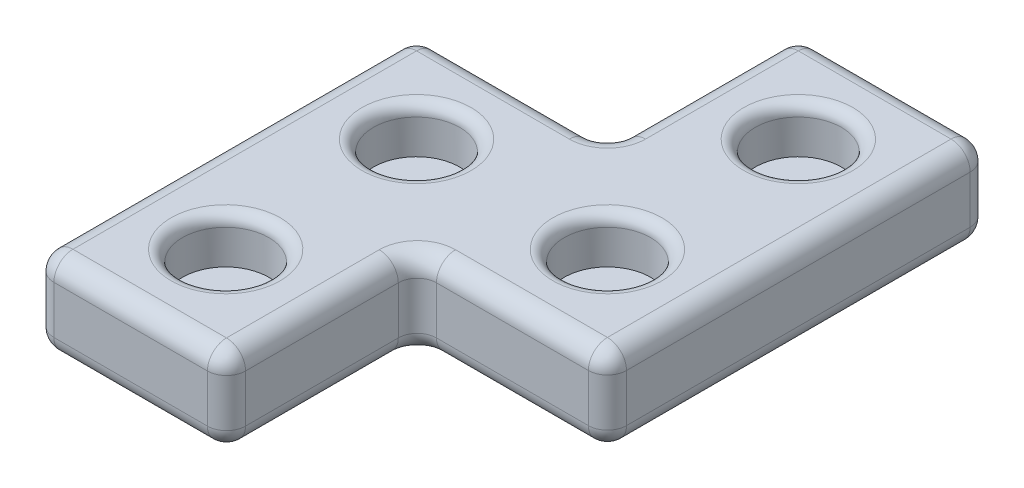
SolidWorks part; units mm, degrees
ref_plane "Front Plane" through (0, 0, 0) normal (0, 0, 1) x (1, 0, 0)
ref_plane "Top Plane" through (0, 0, 0) normal (0, 1, 0) x (1, 0, 0)
ref_plane "Right Plane" through (0, 0, 0) normal (1, 0, 0) x (0, 0, -1)
sketch "Sketch1" plane through (0, 0, 0) normal (0, 1, 0) x (1, 0, 0)
  line L0 (-7.6659, 2.6651) -> (-7.6659, 12.8251)
  line L1 (-6.3959, 14.0951) -> (3.7641, 14.0951)
  line L2 (5.0341, 12.8251) -> (5.0341, -10.0349)
  line L3 (3.7641, -11.3049) -> (-6.3409, -11.3049)
  line L4 (-7.6109, -12.5749) -> (-7.6109, -22.7349)
  line L5 (-8.8809, -24.0049) -> (-19.0959, -24.0049)
  line L6 (-20.3659, -22.7349) -> (-20.3659, 0.1251)
  line L7 (-19.0959, 1.3951) -> (-8.9359, 1.3951)
  arc A0 (-7.6659, 2.6651) -> (-8.9359, 1.3951) centre (-8.9359, 2.6651) cw
  arc A1 (-6.3409, -11.3049) -> (-7.6109, -12.5749) centre (-6.3409, -12.5749) ccw
  arc A2 (-7.6109, -22.7349) -> (-8.8809, -24.0049) centre (-8.8809, -22.7349) cw
  arc A3 (-19.0959, -24.0049) -> (-20.3659, -22.7349) centre (-19.0959, -22.7349) cw
  arc A4 (-20.3659, 0.1251) -> (-19.0959, 1.3951) centre (-19.0959, 0.1251) cw
  arc A5 (5.0341, -10.0349) -> (3.7641, -11.3049) centre (3.7641, -10.0349) cw
  arc A6 (-7.6659, 12.8251) -> (-6.3959, 14.0951) centre (-6.3959, 12.8251) cw
  arc A7 (3.7641, 14.0951) -> (5.0341, 12.8251) centre (3.7641, 12.8251) cw
  point P10 (-7.6659, 1.3951)
  point P13 (-7.6109, -11.3049)
  point P18 (-20.3659, -24.0049)
  point P21 (-20.3659, 1.3951)
  point P24 (5.0341, -11.3049)
  point P27 (-7.6659, 14.0951)
  point P30 (5.0341, 14.0951)
  dimension "D7" = 1.27
  dimension "D1" = 12.7
  dimension "D2" = 25.4
  dimension "D3" = 12.7
  dimension "D4" = 25.4
  dimension "D5" = 12.645
  dimension "D6" = 12.7
extrude "Boss-Extrude1" add sketch "Sketch1" along normal blind 5.715
sketch "Sketch2" plane through (0, 5.715, 0) normal (0, 1, 0) x (1, 0, 0)
  line L0 (5.0341, -10.0349) -> (5.0341, 12.8251) construction
  line L1 (-19.0959, -24.0049) -> (-8.8809, -24.0049) construction
  circle A0 centre (-1.3159, 7.7451) radius 2.8702
  circle A1 centre (-14.0159, -4.9549) radius 2.8702
  circle A2 centre (-14.0159, -17.6549) radius 2.8702
  circle A3 centre (-1.3159, -4.9549) radius 2.8702
  dimension "D1" = 6.35
  dimension "D2" = 12.7
  dimension "D3" = 12.7
  dimension "D4" = 12.7
  dimension "D5" = 6.35
extrude "Cut-Extrude1" cut sketch "Sketch2" against normal blind 3.048
fillet "Fillet1" radius 1.27 16 edges at (-1.2884, 5.715, 11.3049) (-7.6109, 5.715, 17.6549) (-13.9884, 5.715, 24.0049) (-20.3659, 5.715, 11.3049) (-14.0159, 5.715, -1.3951) (-7.6659, 5.715, -7.7451) (-1.3159, 5.715, -14.0951) (5.0341, 5.715, -1.3951) (4.6621, 5.715, 10.9329) (-7.2389, 5.715, 11.6769) (-7.9829, 5.715, 23.6329) (-19.9939, 5.715, 23.6329) (-19.9939, 5.715, -1.0231) (-8.0379, 5.715, -1.7671) (-7.2939, 5.715, -13.7231) (4.6621, 5.715, -13.7231)
fillet "Fillet2" radius 1.27 16 edges at (-1.3159, 0, -14.0951) (-7.6659, 0, -7.7451) (-14.0159, 0, -1.3951) (-20.3659, 0, 11.3049) (-13.9884, 0, 24.0049) (-7.6109, 0, 17.6549) (-1.2884, 0, 11.3049) (5.0341, 0, -1.3951) (4.6621, 0, 10.9329) (-7.2389, 0, 11.6769) (-7.9829, 0, 23.6329) (-19.9939, 0, 23.6329) (-19.9939, 0, -1.0231) (-8.0379, 0, -1.7671) (-7.2939, 0, -13.7231) (4.6621, 0, -13.7231)
fillet "Fillet3" radius 0.762 4 edges at (-14.0159, 5.715, 20.5251) (-14.0159, 5.715, 7.8251) (-1.3159, 5.715, 7.8251) (-1.3159, 5.715, -4.8749)
